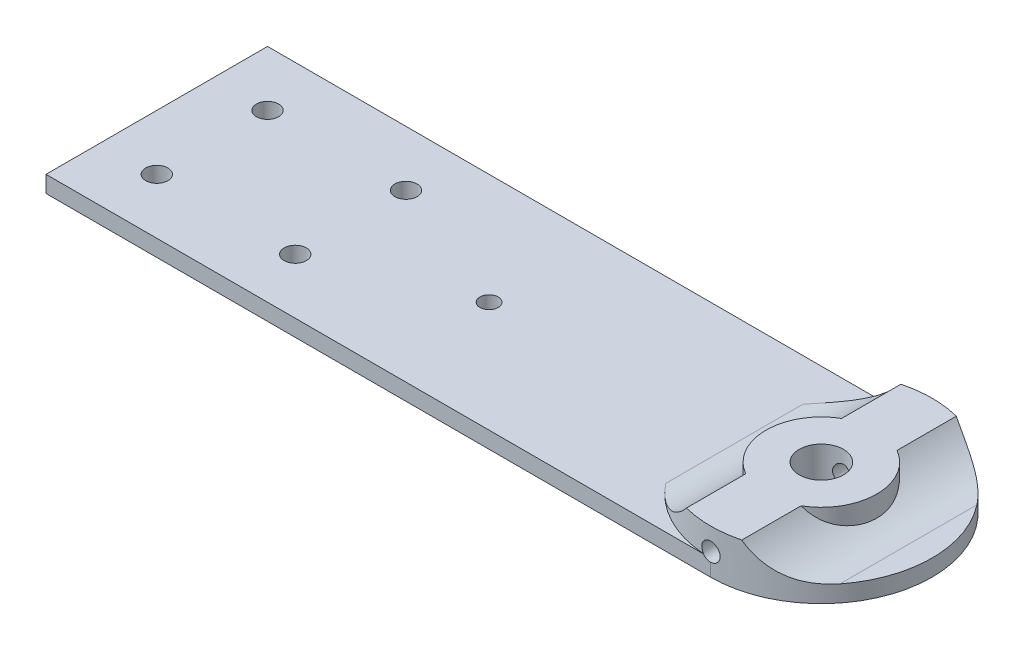
SolidWorks part; units mm, degrees
material "3.3535 (EN-AW 5754)"
ref_plane "Front Plane" through (0, 0, 0) normal (0, 0, 1) x (1, 0, 0)
ref_plane "Top Plane" through (0, 0, 0) normal (0, 1, 0) x (1, 0, 0)
ref_plane "Right Plane" through (0, 0, 0) normal (1, 0, 0) x (0, 0, -1)
sketch "Sketch1" plane through (0, 0, 0) normal (0, 1, 0) x (1, 0, 0)
  line L0 (-120, 20) -> (20, 20)
  line L1 (20, 20) -> (20, -5)
  line L2 (20, -5) -> (-120, -5) construction
  line L3 (-120, -5) -> (-120, 20)
  line L4 (20, -5) -> (20, -20)
  line L5 (20, -20) -> (-120, -20)
  line L6 (-120, -20) -> (-120, -5)
  line L7 (20, -10) -> (-110, -10) construction
  line L8 (-110, -10) -> (-110, -5) construction
  line L9 (-110, -5) -> (-110, 10) construction
  line L10 (-110, 10) -> (20, 10) construction
  circle A0 centre (0, 0) radius 4
  circle A1 centre (-110, 10) radius 2
  circle A2 centre (-85, 10) radius 2
  circle A3 centre (-85, -10) radius 2
  circle A4 centre (-110, -10) radius 2
  arc A5 (0, -20) -> (0, 20) centre (0, 0) ccw
  dimension "D1" = 8
  dimension "D7" = 4
  dimension "D2" = 20
  dimension "D3" = 25
  dimension "D4" = 20
  dimension "D5" = 15
  dimension "D6" = 140
  dimension "D9" = 25
  dimension "D8" = 10
extrude "Boss-Extrude1" add sketch "Sketch1" along normal blind 8 contours L5 A5 L0 L3 L6 A4 A3 A2 A1 A0
sketch "Sketch4" plane through (0, 8, 0) normal (0, 1, 0) x (1, 0, 0)
  line L0 (-5, 20) -> (-120, 20)
  line L1 (-120, 20) -> (-120, -20)
  line L2 (-120, -20) -> (-5, -20)
  line L3 (-120, 20) -> (0, 20) construction
  line L4 (0, -20) -> (-120, -20) construction
  line L5 (-5, 20) -> (-5, 8.6603)
  line L6 (-5, -8.6603) -> (-5, -20)
  line L7 (5, 19.3649) -> (5, 8.6603)
  line L8 (5, -8.6603) -> (5, -19.3649)
  arc A3 (5, -8.6603) -> (5, 8.6603) centre (0, 0) ccw
  arc A4 (0, -20) -> (0, 20) centre (0, 0) ccw construction
  arc A5 (-5, 8.6603) -> (-5, -8.6603) centre (0, 0) ccw
  circle M1 centre (-110, -10) radius 2
  circle M2 centre (-85, -10) radius 2
  circle M3 centre (-85, 10) radius 2
  circle M4 centre (-110, 10) radius 2
  line M6 (-120, -20) -> (0, -20)
  arc M7 (0, -20) -> (0, 20) centre (0, 0) ccw
  line M8 (0, 20) -> (-120, 20)
  line M9 (-120, 20) -> (-120, -20)
  dimension "D1" = 20
  dimension "D2" = 5
  dimension "D3" = 5
extrude "Cut-Extrude1" cut sketch "Sketch4" against normal offset from surface (5 mm away) 3 contours A5 L5 L6 M8 M9 M6 M2 M4 M3 M1 | A3 L8 L7 M7 up to face at (-110, 0, 12)
fillet "Fillet2" radius 14 2 edges at (-5, 3, -14.3301) (5, 3, -14.0126)
hole_wizard "M4 Tapped Hole1" positions "Sketch2" profile "Sketch3" tap size "M4" standard "ISO" end condition through all
sketch "Sketch2" plane through (0, 0, -20) normal (0, 0, -1) x (-1, 0, 0)
  line L0 (0, 55) -> (0, -55) construction
  line L1 (0, 8) -> (0, 0) construction
  point P0 (0, 4)
  point P11 (0, 4)
cosmetic thread "Hole Thread1" parameters "D2"=4
sketch "Sketch3" plane through (0, 4, -20) normal (1, 0, 0) x (0, 1, 0)
  line L0 (0, 0) -> (0, 40)
  line L1 (0, 40) -> (1.65, 40)
  line L2 (1.65, 40) -> (1.65, 0)
  line L5 (1.65, 0) -> (0, 0)
  line L11 (0, -6.35) -> (0, 107.95) construction
  dimension "Thru Tap Drill Dia." = 3.3
  dimension "Thru Tap Drill Depth" = 40
sketch "Sketch5" plane through (0, 3, 0) normal (0, 1, 0) x (1, 0, 0)
  circle A1 centre (-60, 0) radius 1.65
  dimension "D1" = 3.3
extrude "Cut-Extrude2" cut sketch "Sketch5" against normal through all
sketch "Sketch6" plane through (0, 8, 0) normal (0, 1, 0) x (1, 0, 0)
  line L6 (-120, -20) -> (0, -20)
  line L7 (-120, 20) -> (-120, -20)
  line L8 (0, 20) -> (-120, 20)
  line L9 (-120, -20) -> (0, -20)
  line L10 (-120, 20) -> (-120, -20)
  line L11 (0, 20) -> (-120, 20)
  arc A0 (0, 20) -> (0, -20) centre (0, 0) ccw
  arc A1 (0, -20) -> (0, 20) centre (0, 0) ccw construction
  arc A4 (0, -20) -> (0, 20) centre (0, 0) ccw
  dimension "D1" = 0
extrude "Cut-Extrude3" cut sketch "Sketch6" against normal up to surface (5 mm away) up to face at (-60, 3, 1.65)
